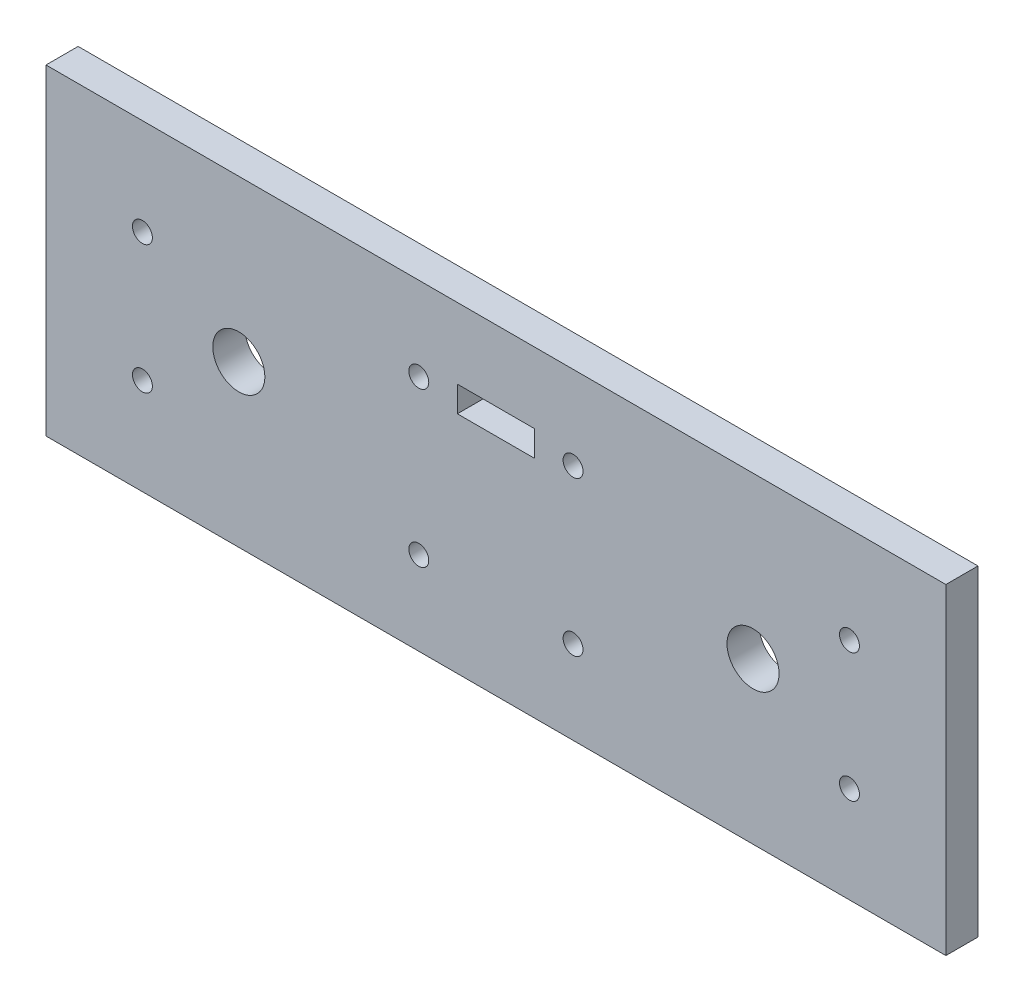
SolidWorks part; units mm, degrees
ref_plane "Plan de face" through (0, 0, 0) normal (0, 0, 1) x (1, 0, 0)
ref_plane "Plan de dessus" through (0, 0, 0) normal (0, 1, 0) x (1, 0, 0)
ref_plane "Plan de droite" through (0, 0, 0) normal (1, 0, 0) x (0, 0, -1)
sketch "Esquisse1" plane through (0, 0, 0) normal (0, 0, 1) x (1, 0, 0)
  line L0 (0, 0) -> (10.6959, 0) construction
  line L1 (-70, -25) -> (70, -25)
  line L2 (-70, -25) -> (-70, 25)
  line L3 (-70, 25) -> (70, 25)
  line L4 (70, -25) -> (70, 25)
  line L5 (-70, -25) -> (70, 25) construction
  line L6 (-70, 25) -> (70, -25) construction
  line L11 (0, 12) -> (0, 0) construction
  line L12 (-6, 10) -> (6, 10)
  line L13 (0, 0) -> (0, -12.4048) construction
  line L14 (-6, 10) -> (-6, 14)
  line L15 (-6, 14) -> (6, 14)
  line L16 (6, 10) -> (6, 14)
  line L17 (-6, 10) -> (6, 14) construction
  line L18 (-6, 14) -> (6, 10) construction
  circle A0 centre (-40, 0) radius 4.05
  circle A6 centre (-55, -10) radius 1.55
  circle A7 centre (-55, 10) radius 1.55
  circle A8 centre (55, -10) radius 1.55
  circle A9 centre (55, 10) radius 1.55
  circle A10 centre (40, 0) radius 4.05
  circle A11 centre (-12, 12) radius 1.55
  circle A12 centre (-12, -12) radius 1.55
  circle A13 centre (12, -12) radius 1.55
  circle A14 centre (12, 12) radius 1.55
  point P0 (0, 0)
  point P5 (0, 0)
  point P8 (0, 12)
  point P36 (0, 0)
  dimension "D3" = 15
  dimension "D4" = 15
  dimension "D5" = 8.1
  dimension "D6" = 3.1
  dimension "D7" = 3.1
  dimension "D1" = 140
  dimension "D2" = 50
  dimension "D8" = 12
  dimension "D9" = 40
  dimension "D10" = 12
  dimension "D11" = 12
  dimension "D12" = 4
  dimension "D13" = 12
  dimension "D14" = 25
extrude "Boss.-Extru.1" add sketch "Esquisse1" against normal blind 5
